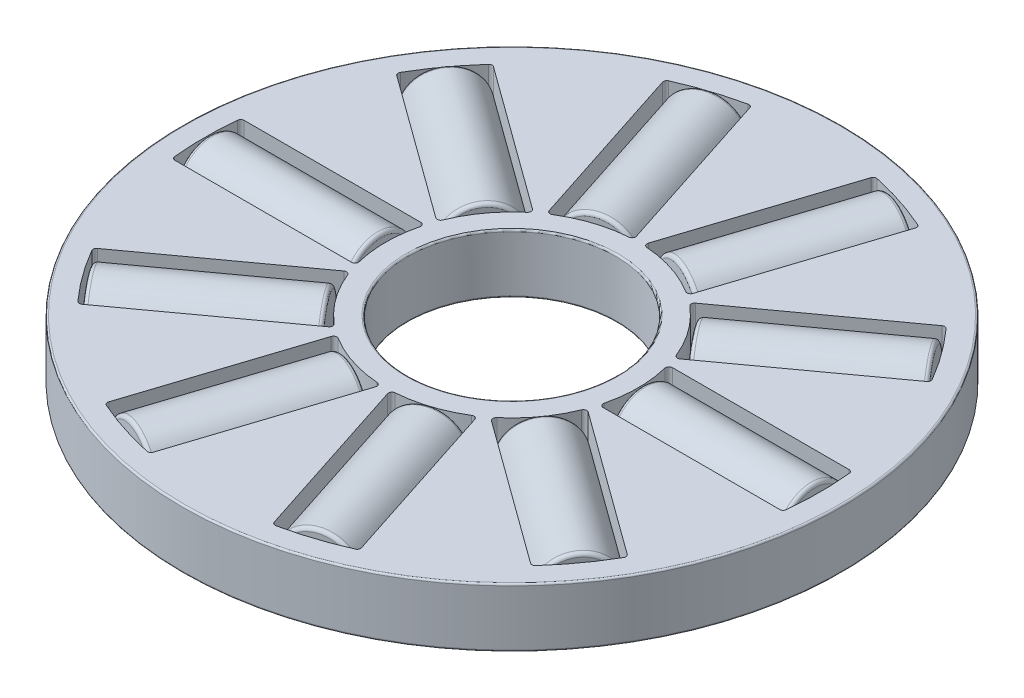
SolidWorks part; units mm, degrees
material "Alloy Steel"
ref_plane "Front Plane" through (0, 0, 0) normal (0, 0, 1) x (1, 0, 0)
ref_plane "Top Plane" through (0, 0, 0) normal (0, 1, 0) x (1, 0, 0)
ref_plane "Right Plane" through (0, 0, 0) normal (1, 0, 0) x (0, 0, -1)
sketch "Sketch1" plane through (0, 0, 0) normal (1, 0, 0) x (0, 0, -1)
  line L0 (-9.5, 0) -> (9.5, 0) construction
  line L1 (-3.01, 0) -> (3.01, 0) construction
  line L2 (9.5, -1) -> (9.5, 1) construction
  line L3 (3.01, -0.85) -> (3.01, 0.85) construction
  line L23 (9, 0.85) -> (9.5, 0.85) construction
  line L32 (0, 1) -> (0, -1) construction
  line L33 (-3.5, 1) -> (3.5, 1) construction
  line L34 (-9, 0.85) -> (9, 0.85) construction
  point P4 (0, 0)
  point P8 (0, 0)
  point P11 (9.5, 0)
  point P14 (3.01, 0)
  point P45 (0, 1)
  point P48 (0, 0)
  point P49 (0, 1)
  point P55 (0, 0.85)
  dimension "OD" = 19
  dimension "ID" = 6.02
  dimension "Thickness" = 2
  dimension "Approx. Raceway Thickness" = 1.7
  dimension "Inner Raceway" = 7
  dimension "Outer Raceway" = 18
sketch "Sketch2" plane through (0, 0, 0) normal (0, 1, 0) x (1, 0, 0)
  line L0 (3.5, 0) -> (9, 0) construction
  line L1 (8.8625, 0) -> (3.6375, 0)
  line L2 (8.8061, -0.9979) -> (3.4979, -0.9979)
  line L3 (8.8061, 0.9979) -> (3.4979, 0.9979)
  circle A0 centre (0, 0) radius 3.01
  circle A1 centre (0, 0) radius 3.5
  circle A2 centre (0, 0) radius 9
  circle A3 centre (0, 0) radius 9.5
  arc A4 (3.4979, -0.9979) -> (3.4979, 0.9979) centre (0, 0) ccw
  arc A5 (8.8061, -0.9979) -> (8.8061, 0.9979) centre (0, 0) ccw
  arc A6 (8.8061, 0.9979) -> (8.4239, 2.7537) centre (0, 0) ccw
  point P15 (6.25, 0)
  dimension "Approx. Roller Seat Length" = 5.225
  dimension "Roller Width" = 2
  dimension "Approx. Roller Gap" = 1.8
sketch "Sketch3" plane through (0, 0, 0) normal (1, 0, 0) x (0, 0, -1)
  line L24 (9.5, -1) -> (9.5, 1) construction
  line L25 (3.01, 0.85) -> (9.5, 0.85)
  line L26 (3.01, 0.85) -> (3.01, -0.85)
  line L27 (3.01, -0.85) -> (9.5, -0.85)
  line L28 (9.5, 0.85) -> (9.5, -0.85)
revolve "Revolve1" add sketch "Sketch3" angle 360 about L32
fillet "Fillet1" radius 0.05 4 edges at (0, -0.85, 3.01) (0, -0.85, 9.5) (0, 0.85, 9.5) (0, 0.85, 3.01)
sketch "Sketch4" plane through (0, 0, 0) normal (0, 1, 0) x (1, 0, 0)
  line L0 (3.4979, 0.9979) -> (8.8061, 0.9979)
  line L1 (3.4979, -0.9979) -> (8.8061, -0.9979)
  arc A0 (3.4979, -0.9979) -> (3.4979, 0.9979) centre (0, 0) ccw construction
  arc A1 (3.4979, -0.9979) -> (3.4979, 0.9979) centre (0, 0) ccw
  arc A2 (8.8061, -0.9979) -> (8.8061, 0.9979) centre (0, 0) ccw construction
  arc A3 (8.8061, -0.9979) -> (8.8061, 0.9979) centre (0, 0) ccw
extrude "Cut-Extrude1" cut sketch "Sketch4" against normal through all both and the other way through all
fillet "Fillet5" radius 0.1 4 edges at (8.8061, 0, -0.9979) (8.8061, 0, 0.9979) (3.4979, 0, -0.9979) (3.4979, 0, 0.9979)
pattern_circular "CirPattern1" count 10 over 360 about axis through (0, 1, 0) along (0, -1, 0) of "Cut-Extrude1", "Fillet5"
sketch "Sketch5" plane through (0, 0, 0) normal (0, 1, 0) x (1, 0, 0)
  line L0 (3.7681, 0) -> (3.7681, 0.9979)
  line L1 (8.8061, 0.9979) -> (3.4979, 0.9979) construction
  line L2 (3.7681, 0.9979) -> (8.7319, 0.9979)
  line L3 (8.7319, 0.9979) -> (8.7319, 0)
  line L4 (8.7319, 0) -> (3.7681, 0)
  line L6 (8.8625, 0) -> (3.6375, 0) construction
  dimension "D1" = 4.9637
revolve "Revolve2" add sketch "Sketch5" angle 360 about L1
fillet "Fillet6" radius 0.1 2 edges at (3.7681, 0, -0.9979) (8.7319, 0, -0.9979)
pattern_circular "CirPattern2" count 10 over 360 about axis through (0, 1, 0) along (0, -1, 0) of bodies 107
ref_axis "Center Axis 1" through (0, -1.0981, 0) along (0, 1, 0)
ref_plane "Contact Plane 1" through (0, 1, 0) normal (0, 1, 0) x (1, 0, 0)
ref_plane "Contact Plane 2" through (0, -1, 0) normal (0, 1, 0) x (1, 0, 0)
equation "\"Approx. Raceway Thickness@Sketch1\" = \"Thickness@Sketch1\" * .85"
equation "\"D1@Fillet1\"=\"Thickness@Sketch1\" * .025"
equation "\"Approx. Roller Seat Length@Sketch2\" = \"Raceway Diff\" / 2 * .95"
equation "\"Approx. Roller Gap@Sketch2\" = \"Roller Width@Sketch2\" * .9"
equation "\"Raceway Diff\"= ( \"Outer Raceway@Sketch1\" - \"Inner Raceway@Sketch1\" )"
equation "\"Circumference\"= ( \"Inner Raceway@Sketch1\" + ( \"Raceway Diff\" / 2 ) ) * 3.14"
equation "\"Instances\"= int ( \"Circumference\" /  ( \"Roller Width@Sketch2\" + \"Approx. Roller Gap@Sketch2\" )  ) "
equation "\"D1@CirPattern1\"=\"Instances\""
equation "\"Roller Width@Sketch2\" = \"Thickness@Sketch1\""
equation "\"D1@Fillet5\" = \"Roller Width@Sketch2\" / 20"
equation "\"D1@Fillet6\" = \"Roller Width@Sketch2\" / 20"
equation "\"D1@CirPattern2\" = \"D1@CirPattern1\""
equation "\"D1@Sketch5\" = \"Approx. Roller Seat Length@Sketch2\" * .95"
